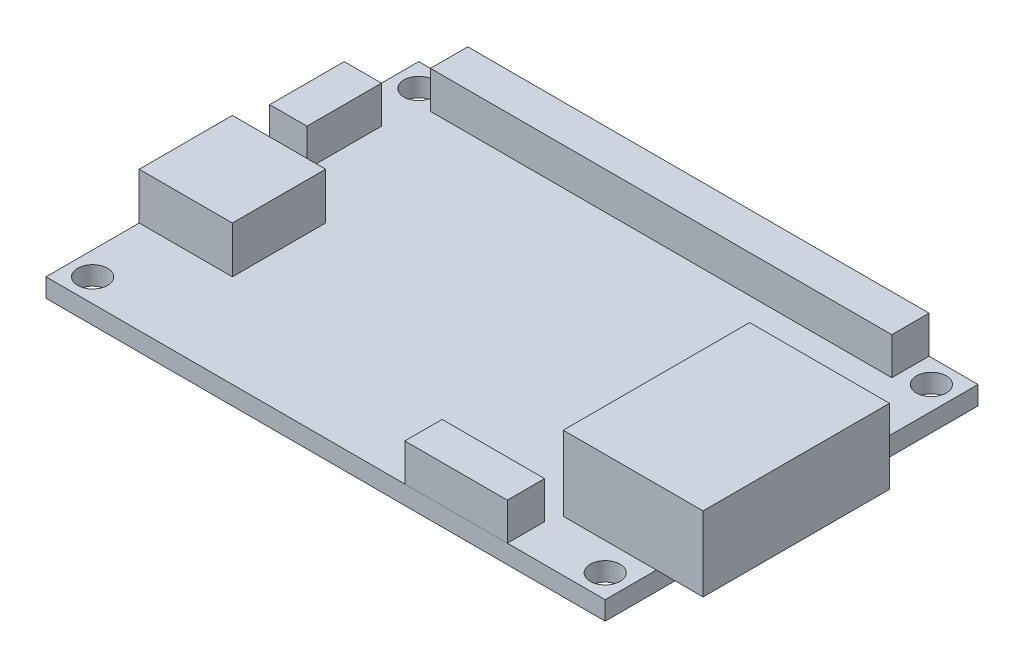
SolidWorks part; units mm, degrees
ref_plane "前视基准面" through (0, 0, 0) normal (0, 0, 1) x (1, 0, 0)
ref_plane "上视基准面" through (0, 0, 0) normal (0, 1, 0) x (1, 0, 0)
ref_plane "右视基准面" through (0, 0, 0) normal (1, 0, 0) x (0, 0, -1)
other "Configuration Table"
sketch "草图1" plane through (0, 0, 0) normal (0, 1, 0) x (1, 0, 0)
  line L0 (0, 40.1762) -> (0, -49.8238) construction
  line L1 (-30, -20) -> (30, -20)
  line L2 (-30, -20) -> (-30, 20)
  line L3 (-30, 20) -> (30, 20)
  line L4 (30, -20) -> (30, 20)
  line L5 (-30, -20) -> (30, 20) construction
  line L6 (-30, 20) -> (30, -20) construction
  line L7 (-58.2819, 0) -> (54.7137, 0) construction
  circle A0 centre (-27.5, 17.5) radius 1.6
  circle A1 centre (27.5, 17.5) radius 1.6
  circle A2 centre (27.5, -17.5) radius 1.6
  circle A3 centre (-27.5, -17.5) radius 1.6
  point P0 (0, 0)
  dimension "D3" = 3.2
  dimension "D4" = 55
  dimension "D1" = 60
  dimension "D2" = 40
  dimension "D5" = 35
extrude "凸台-拉伸1" add sketch "草图1" along normal blind 2 contours L3 L4 L1 L2 | A3 | A2 | A1 | A0
sketch "草图2" plane through (0, 2, 0) normal (0, 1, 0) x (1, 0, 0)
  line L0 (-30, 20) -> (30, 20) construction
  line L1 (-24.75, 20) -> (24.75, 20)
  line L2 (-24.75, 20) -> (-24.75, 16)
  line L3 (-24.75, 16) -> (24.75, 16)
  line L4 (24.75, 20) -> (24.75, 16)
  line L6 (35, 5.5) -> (20, 5.5)
  line L7 (35, 5.5) -> (35, -14.5)
  line L8 (35, -14.5) -> (20, -14.5)
  line L9 (20, 5.5) -> (20, -14.5)
  line L10 (-30, -20) -> (-30, 20) construction
  line L11 (-30, 12) -> (-26, 12)
  line L12 (-30, 12) -> (-30, 4)
  line L13 (-30, 4) -> (-26, 4)
  line L14 (-26, 12) -> (-26, 4)
  line L15 (-30, -20) -> (30, -20) construction
  line L16 (-30, 0) -> (-20, 0)
  line L17 (-30, 0) -> (-30, -10)
  line L18 (-30, -10) -> (-20, -10)
  line L19 (-20, 0) -> (-20, -10)
  line L20 (8.5, -16) -> (19.5, -16)
  line L21 (8.5, -16) -> (8.5, -20)
  line L22 (8.5, -20) -> (19.5, -20)
  line L23 (19.5, -16) -> (19.5, -20)
  line L24 (0, 16) -> (0, 0) construction
  line L25 (30, -20) -> (30, 20) construction
  line L31 (-30, 20) -> (-30, -20)
  line L32 (-30, -20) -> (30, -20)
  line L33 (30, -20) -> (30, 20)
  line L34 (30, 20) -> (-30, 20)
  line L35 (-30, 20) -> (-30, -20) construction
  line L36 (-30, -20) -> (30, -20) construction
  line L37 (30, -20) -> (30, 20) construction
  line L38 (30, 20) -> (-30, 20) construction
  circle A1 centre (27.5, -17.5) radius 1.6 construction
  circle A2 centre (27.5, -17.5) radius 1.6 construction
  circle A3 centre (27.5, 17.5) radius 1.6 construction
  circle A4 centre (27.5, 17.5) radius 1.6 construction
  point P34 (-28, 12)
  line M30 (-30, 20) -> (-30, -20)
  line M32 (30, -20) -> (30, 20)
  dimension "D6" = 0
  dimension "D1" = 4
  dimension "D2" = 49.5
  dimension "D3" = 20
  dimension "D4" = 10
  dimension "D5" = 5
  dimension "D7" = 3
  dimension "D8" = 8
  dimension "D9" = 11
  dimension "D10" = 4
  dimension "D11" = 8
  dimension "D12" = 8
  dimension "D13" = 4
  dimension "D14" = 10
  dimension "D15" = 10
  dimension "D16" = 10
extrude "凸台-拉伸2" add sketch "草图2" along normal blind 4 separate body contours L3 L4 L1 L2 | L14 L13 L12 L11 | L20 L23 L22 L21
extrude "凸台-拉伸3" add sketch "草图2<3>" along normal blind 5 separate body contours L19 L16 L18 M30 region at (-25, 2, 5)
sketch "草图2<3>" plane through (0, 2, 0) normal (0, 1, 0) x (1, 0, 0) same geometry as "草图2"
extrude "凸台-拉伸4" add sketch "草图2<4>" along normal blind 8 separate body contours L8 L7 L6 M32 | L6 L9 L8 M32 region at (25, 2, 4.5) region at (32.5, 2, 4.5)
sketch "草图2<4>" plane through (0, 2, 0) normal (0, 1, 0) x (1, 0, 0) same geometry as "草图2"
